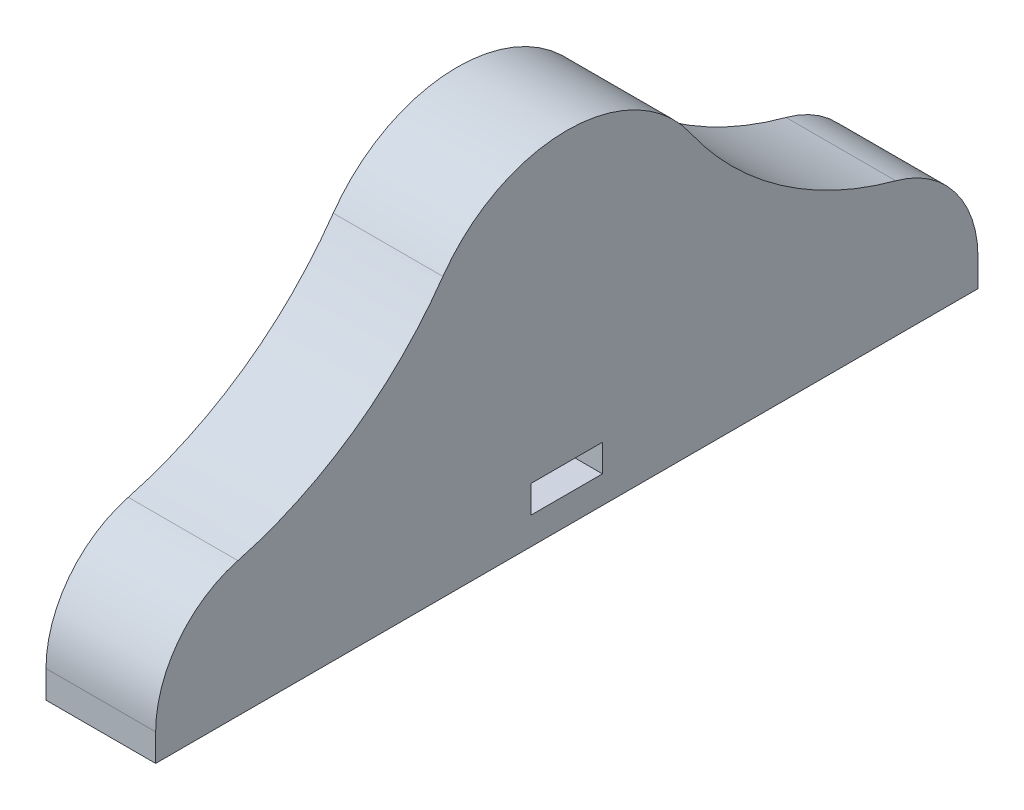
SolidWorks part; units mm, degrees
ref_plane "Front Plane" through (0, 0, 0) normal (0, 0, 1) x (1, 0, 0)
ref_plane "Top Plane" through (0, 0, 0) normal (0, 1, 0) x (1, 0, 0)
ref_plane "Right Plane" through (0, 0, 0) normal (1, 0, 0) x (0, 0, -1)
sketch "Sketch1" plane through (0, 0, 0) normal (1, 0, 0) x (0, 0, -1)
  line L0 (0, 0) -> (60, 0)
  line L1 (60, 0) -> (60, 2)
  line L2 (0, 0) -> (0, 2)
  line L3 (30, 0) -> (30, 27.8113) construction
  line L4 (30, 13.9616) -> (18.336, 22.1288) construction
  line L5 (-4.7429, 6.9408) -> (16.2966, 12.5783) construction
  line L6 (0, 2) -> (27.4, 2) construction
  line L7 (27.4, 2) -> (32.6, 2)
  line L8 (27.4, 2) -> (27.4, 4)
  line L9 (27.4, 4) -> (32.6, 4)
  line L10 (32.6, 2) -> (32.6, 4)
  arc A0 (20.9579, 20.293) -> (39.0421, 20.293) centre (30, 13.9616) cw
  arc A1 (0, 2) -> (6, 9.8194) centre (8.0952, 2) cw
  arc A2 (6, 9.8194) -> (20.9579, 20.293) centre (-0.9091, 35.6044) ccw
  arc A3 (60, 2) -> (54, 9.8194) centre (51.9048, 2) ccw
  arc A4 (54, 9.8194) -> (39.0421, 20.293) centre (60.9091, 35.6044) cw
  point P11 (30, 25)
  point P18 (30, 4)
  point P19 (0, 0)
  point P26 (50.9242, 0)
  dimension "D1" = 55
  dimension "D2" = 15
  dimension "D3" = 60
  dimension "D4" = 2
  dimension "D5" = 6
  dimension "D6" = 25
  dimension "D7" = 5.2
  dimension "D8" = 2
extrude "Boss-Extrude1" add sketch "Sketch1" against normal blind 8
